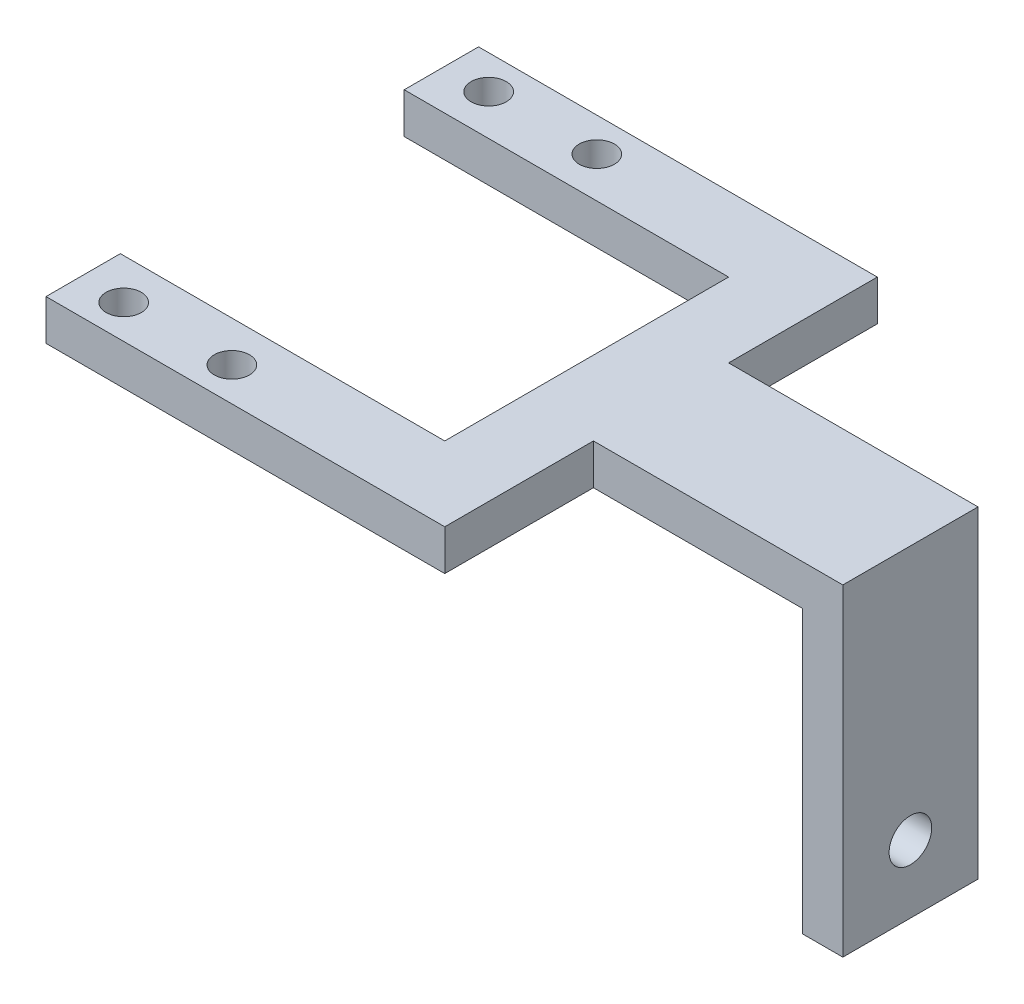
SolidWorks part; units mm, degrees
ref_plane "Front Plane" through (0, 0, 0) normal (0, 0, 1) x (1, 0, 0)
ref_plane "Top Plane" through (0, 0, 0) normal (0, 1, 0) x (1, 0, 0)
ref_plane "Right Plane" through (0, 0, 0) normal (1, 0, 0) x (0, 0, -1)
sketch "Sketch1" plane through (0, 0, 0) normal (0, 1, 0) x (1, 0, 0)
  line L0 (-14.75, 10.5) -> (9.25, 10.5)
  line L1 (14.75, 16) -> (-14.75, 16)
  line L2 (14.75, 16) -> (14.75, 5)
  line L3 (14.75, -16) -> (-14.75, -16)
  line L4 (-14.75, 16) -> (-14.75, 10.5)
  line L5 (14.75, 16) -> (-14.75, -16) construction
  line L6 (14.75, -16) -> (-14.75, 16) construction
  line L7 (9.25, 10.5) -> (9.25, -10.5)
  line L8 (9.25, -10.5) -> (-14.75, -10.5)
  line L9 (-14.75, -10.5) -> (-14.75, -16)
  line L10 (14.75, -5) -> (14.75, -16)
  line L11 (14.75, 5) -> (33.2, 5)
  line L13 (14.75, -5) -> (33.2, -5)
  line L14 (33.2, 5) -> (33.2, -5)
  line L15 (33.2, 5) -> (30.2, 5)
  line L16 (33.2, 5) -> (33.2, -5)
  line L17 (33.2, -5) -> (30.2, -5)
  line L18 (30.2, 5) -> (30.2, -5)
  line L19 (-13.1175, 0) -> (13.1175, 0) construction
  circle A0 centre (-11.5, -13.5) radius 1.3
  circle A1 centre (-3.5, -13.5) radius 1.3
  circle A2 centre (-3.5, 13.5) radius 1.3
  circle A3 centre (-11.5, 13.5) radius 1.3
  point P0 (0, 0)
  point P14 (33.2, 0)
  point P21 (0, 0)
  dimension "D10" = 2.6
  dimension "D1" = 5.5
  dimension "D2" = 5.5
  dimension "D3" = 29.5
  dimension "D4" = 5.5
  dimension "D5" = 32
  dimension "D6" = 18.45
  dimension "D7" = 10
  dimension "D8" = 3
  dimension "D9" = 3.25
  dimension "D11" = 8
  dimension "D12" = 2.5
extrude "Boss-Extrude2" add sketch "Sketch1" against normal blind 3 contours L18 L11 L2 L1 L4 L0 L7 L8 L9 L3 L10 L13 | L11 L18 L13 L14 region at (-14.1982, 0, -13.25) region at (31.7, 0, 0)
extrude "Boss-Extrude3" add sketch "Sketch1<5>" against normal blind 23.85 contours L11 L18 L13 L14 region at (31.7, 0, 0)
sketch "Sketch1<5>" plane through (0, 0, 0) normal (0, 1, 0) x (1, 0, 0) same geometry as "Sketch1"
sketch "Sketch4" plane through (30.2, 0, 0) normal (-1, 0, 0) x (0, 0, 1)
  line L0 (-5, -23.85) -> (5, -23.85) construction
  line L2 (-5, -3) -> (5, -3) construction
  circle A0 centre (0, -18.85) radius 1.5754
  point P4 (0, -23.85)
  dimension "D1" = 3.1508
  dimension "D2" = 15.85
extrude "Cut-Extrude1" cut sketch "Sketch4" against normal up to surface (3 mm away) up to face at (33.2, -11.925, 0)
